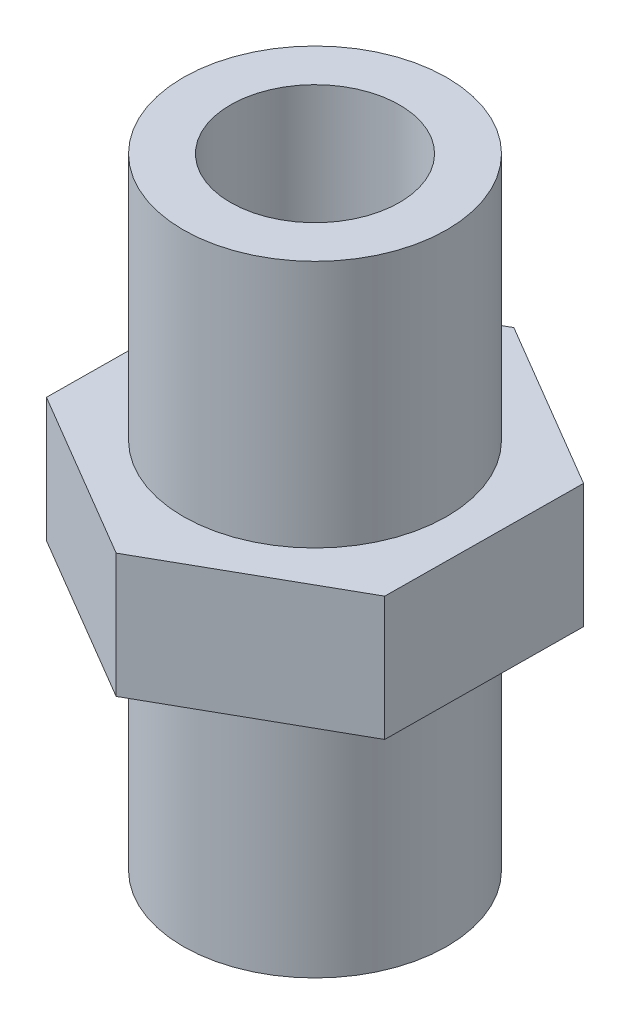
SolidWorks part; units mm, degrees
material "AISI 316  (SS)"
ref_plane "Front Plane" through (0, 0, 0) normal (0, 0, 1) x (1, 0, 0)
ref_plane "Top Plane" through (0, 0, 0) normal (0, 1, 0) x (1, 0, 0)
ref_plane "Right Plane" through (0, 0, 0) normal (1, 0, 0) x (0, 0, -1)
sketch "Sketch1" plane through (0, 0, 0) normal (0, 1, 0) x (1, 0, 0)
  circle A0 centre (0, 0) radius 8.5
  dimension "D1" = 17
extrude "Boss-Extrude1" add sketch "Sketch1" along normal mid plane 40
sketch "Sketch2" plane through (0, 0, 0) normal (0, 1, 0) x (1, 0, 0)
  line L1 (11.0565, 6.252) -> (0.1139, 12.7012)
  line L2 (0.1139, 12.7012) -> (-10.9426, 6.4492)
  line L3 (-10.9426, 6.4492) -> (-11.0565, -6.252)
  line L4 (-11.0565, -6.252) -> (-0.1139, -12.7012)
  line L5 (-0.1139, -12.7012) -> (10.9426, -6.4492)
  line L6 (10.9426, -6.4492) -> (11.0565, 6.252)
  circle A0 centre (0, 0) radius 11 construction
  dimension "D1" = 22
extrude "Boss-Extrude2" add sketch "Sketch2" along normal mid plane 8
sketch "Sketch3" plane through (0, 20, 0) normal (0, 1, 0) x (1, 0, 0)
  circle A0 centre (0, 0) radius 5.45
  dimension "D1" = 10.9
extrude "Cut-Extrude1" cut sketch "Sketch3" against normal through all both and the other way through all
fillet "Fillet1" radius 6 1 edges at (0, -20, 5.45)
